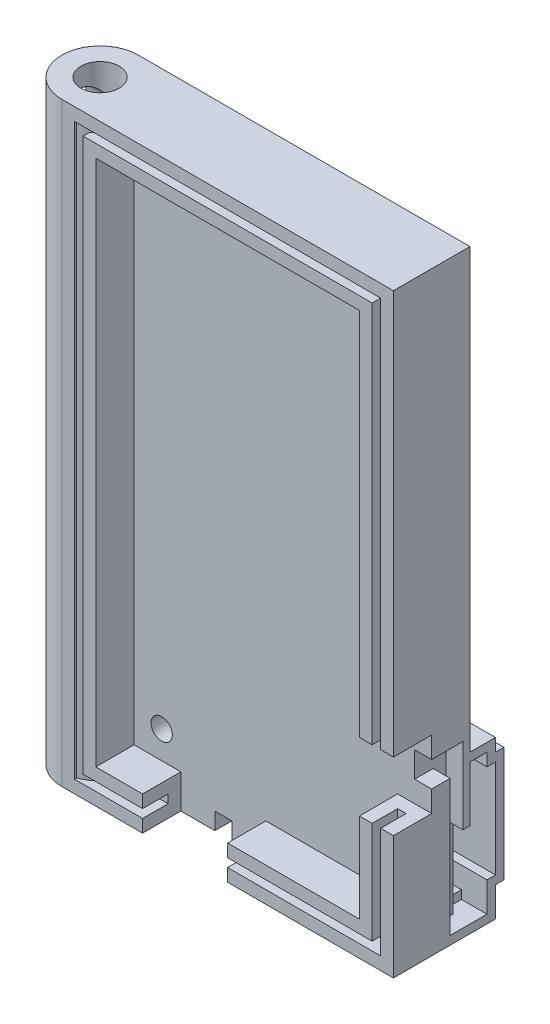
SolidWorks part; units mm, degrees
ref_plane "Front Plane" through (0, 0, 0) normal (0, 0, 1) x (1, 0, 0)
ref_plane "Top Plane" through (0, 0, 0) normal (0, 1, 0) x (1, 0, 0)
ref_plane "Right Plane" through (0, 0, 0) normal (1, 0, 0) x (0, 0, -1)
sketch "Sketch1" plane through (0, 0, 0) normal (0, 0, 1) x (1, 0, 0)
  line L1 (0, 0) -> (39, 0)
  line L2 (0, 0) -> (0, 70)
  line L3 (0, 70) -> (39, 70)
  line L4 (39, 0) -> (39, 70)
  dimension "D1" = 70
  dimension "D2" = 39
extrude "Base" add sketch "Sketch1" along normal blind 4.5
sketch "Sketch2" plane through (0, 0, 4.5) normal (0, 0, 1) x (1, 0, 0)
  line L0 (0, 70) -> (0, 0) construction
  line L1 (39, 70) -> (0, 70)
  line L2 (39, 70) -> (39, 66)
  line L3 (39, 66) -> (0, 66)
  line L4 (0, 70) -> (0, 66)
  line L5 (0, 0) -> (39, 0) construction
  line L6 (0, 66) -> (4, 66)
  line L7 (0, 66) -> (0, 0)
  line L8 (0, 0) -> (4, 0)
  line L9 (4, 66) -> (4, 0)
  line L10 (39, 0) -> (39, 70) construction
  line L11 (4, 0) -> (39, 0)
  line L12 (4, 0) -> (4, 4)
  line L13 (4, 4) -> (39, 4)
  line L14 (39, 0) -> (39, 4)
  line L16 (39, 66) -> (35, 66)
  line L17 (39, 66) -> (39, 4)
  line L18 (39, 4) -> (35, 4)
  line L19 (35, 66) -> (35, 4)
  line M6 (0, 70) -> (0, 0)
  line M7 (0, 0) -> (39, 0)
  line M8 (39, 0) -> (39, 70)
  line M9 (39, 70) -> (0, 70)
  dimension "D1" = 4
  dimension "D2" = 4
  dimension "D3" = 4
  dimension "D4" = 4
extrude "Walls" add sketch "Sketch2" along normal blind 4.5 contours L3 M8 M9 M6 | L3 L19 L13 M8 | L9 L3 M6 M7 | L13 L9 M7 M8 region at (19.5, 68, 4.5) region at (37, 35, 4.5) region at (2, 33, 4.5) region at (21.5, 2, 4.5)
sketch "Sketch3" plane through (0, 4, 0) normal (0, 1, 0) x (1, 0, 0)
  line L0 (4, -4.5) -> (35, -4.5) construction
  line L1 (9.5, -4.5) -> (19.5, -4.5)
  line L2 (9.5, -4.5) -> (9.5, -9)
  line L3 (9.5, -9) -> (19.5, -9)
  line L4 (19.5, -4.5) -> (19.5, -9)
  line L5 (4, -9) -> (35, -9) construction
  line L6 (4, -9) -> (4, -4.5) construction
  dimension "D1" = 5.5
  dimension "D2" = 15.5
extrude "PWR connector hole" cut sketch "Sketch3" against normal blind 4
sketch "Sketch4" plane through (35, 0, 0) normal (-1, 0, 0) x (0, 0, 1)
  line L0 (4.5, 66) -> (4.5, 4) construction
  line L1 (4.5, 14.5) -> (9, 14.5)
  line L2 (4.5, 14.5) -> (4.5, 22.5)
  line L3 (4.5, 22.5) -> (9, 22.5)
  line L4 (9, 14.5) -> (9, 22.5)
  line L5 (9, 66) -> (9, 4) construction
  line L6 (9, 4) -> (4.5, 4) construction
  dimension "D1" = 10.5
  dimension "D2" = 18.5
extrude "GPS connector hole" cut sketch "Sketch4" against normal blind 4
sketch "Sketch5" plane through (0, 0, 4.5) normal (0, 0, 1) x (1, 0, 0)
  line L0 (4, 4) -> (9.5, 4) construction
  line L1 (4, 66) -> (4, 4) construction
  line L2 (19.5, 66) -> (19.5, 4) construction
  line L3 (35, 66) -> (4, 66) construction
  line L5 (19.5, 35) -> (4, 35) construction
  line L6 (4, 66) -> (4, 4) construction
  circle A0 centre (7.25, 7.25) radius 1.25
  circle A1 centre (31.75, 7.25) radius 1.25
  circle A2 centre (7.25, 62.75) radius 1.25
  dimension "D1" = 3.25
  dimension "D3" = 2.5
  dimension "D2" = 3.25
extrude "Mounting holes" cut sketch "Sketch5" against normal blind 4
sketch "Sketch7" plane through (0, 0, 0) normal (0, 0, -1) x (-1, 0, 0)
  line L0 (-39, 0) -> (-39, 18.5) construction
  line L1 (-39, 0) -> (-39, 70) construction
  line L3 (-39, 1) -> (-8, 1)
  line L4 (-39, 1) -> (-39, 17.5)
  line L5 (-39, 17.5) -> (-8, 17.5)
  line L6 (-8, 1) -> (-8, 17.5)
  line L9 (0, 0) -> (-39, 0) construction
  line L10 (-39, 0) -> (-7, 0)
  line L11 (-7, 0) -> (-7, 18.5)
  line L12 (-7, 18.5) -> (-39, 18.5)
  line L13 (-39, 18.5) -> (-39, 17.5)
  line L14 (-39, 1) -> (-39, 0)
  line M8 (-39, 70) -> (-39, 0)
  line M9 (-39, 0) -> (0, 0)
  dimension "D1" = 18.5
  dimension "D2" = 1
  dimension "D3" = 16.5
  dimension "D4" = 31
  dimension "D5" = 32
  dimension "D6" = 18.5
extrude "GPS mount" add sketch "Sketch7" along normal blind 3 contours L11 L12 L5 L6 L3 M8 M9 region at (23.5, 0.6304, 0)
sketch "Sketch8" plane through (8, 0, 0) normal (1, 0, 0) x (0, 0, -1)
  line L0 (3, 17.5) -> (0, 17.5) construction
  line L1 (1, 17.5) -> (2, 17.5)
  line L2 (1, 17.5) -> (1, 16.5)
  line L3 (1, 16.5) -> (2, 16.5)
  line L4 (2, 17.5) -> (2, 16.5)
  line L5 (0, 1) -> (0, 17.5) construction
  line L6 (0, 9.25) -> (3, 9.25) construction
  line L7 (3, 1) -> (3, 17.5) construction
  line L8 (1, 2) -> (2, 2)
  line L9 (2, 1) -> (2, 2)
  line L10 (1, 1) -> (2, 1)
  line L11 (1, 1) -> (1, 2)
  dimension "D1" = 1
  dimension "D2" = 1
  dimension "D3" = 1
extrude "GPS rails" add sketch "Sketch8" along normal blind 28
sketch "Sketch9" plane through (8, 0, 0) normal (1, 0, 0) x (0, 0, -1)
  line L1 (3, 1) -> (2, 1)
  line L2 (3, 1) -> (3, 17.5)
  line L3 (3, 17.5) -> (2, 17.5)
  line L4 (2, 1) -> (2, 17.5)
extrude "GPS \"roof\"" add sketch "Sketch9" along normal blind 14
sketch "Sketch10" plane through (22, 0, 0) normal (1, 0, 0) x (0, 0, -1)
  line L0 (3, 1) -> (3, 17.5) construction
  line L1 (2, 17.5) -> (3, 17.5)
  line L2 (2, 17.5) -> (2, 16)
  line L3 (2, 16) -> (3, 16)
  line L4 (3, 17.5) -> (3, 16)
  line L6 (2, 1) -> (3, 1)
  line L7 (2, 1) -> (2, 4.5)
  line L8 (2, 4.5) -> (3, 4.5)
  line L9 (3, 1) -> (3, 4.5)
  dimension "D1" = 1.5
  dimension "D2" = 3.5
extrude "GPS \"roof" add sketch "Sketch10" along normal blind 17
sketch "Sketch18" plane through (0, 0, -3) normal (0, 0, -1) x (-1, 0, 0)
  line L0 (-22, 4.5) -> (-22, 16) construction
  line L1 (-39, 4.5) -> (-21, 4.5)
  line L2 (-39, 4.5) -> (-39, 3.5)
  line L3 (-39, 3.5) -> (-21, 3.5)
  line L4 (-21, 4.5) -> (-21, 3.5)
  dimension "D1" = 1
  dimension "D2" = 1
extrude "Chip roof1" add sketch "Sketch18" along normal blind 1
sketch "Sketch19" plane through (0, 4.5, 0) normal (0, 1, 0) x (1, 0, 0)
  line L0 (39, 4) -> (39, 2) construction
  line L1 (21, 4) -> (39, 4)
  line L2 (21, 4) -> (21, 3)
  line L3 (21, 3) -> (39, 3)
  line L4 (39, 4) -> (39, 3)
extrude "Chip roof2" add sketch "Sketch19" along normal blind 12.5
sketch "Sketch11" plane through (0, 0, 0) normal (0, 0, -1) x (-1, 0, 0)
  line L0 (0, 0) -> (-7, 0) construction
  line L1 (-4, 0) -> (-5, 0)
  line L2 (-4, 0) -> (-4, 21.5)
  line L3 (-4, 21.5) -> (-5, 21.5)
  line L4 (-5, 0) -> (-5, 21.5)
  line L5 (-7, 0) -> (-7, 18.5) construction
  line L7 (0, 70) -> (0, 0) construction
  line L8 (-5, 21.5) -> (-22, 21.5)
  line L9 (-5, 21.5) -> (-5, 20.5)
  line L10 (-5, 20.5) -> (-22, 20.5)
  line L11 (-22, 21.5) -> (-22, 20.5)
  line L12 (-7, 18.5) -> (-39, 18.5) construction
  line L13 (-28, 18.5) -> (-27, 18.5)
  line L14 (-28, 18.5) -> (-28, 21.5)
  line L15 (-28, 21.5) -> (-27, 21.5)
  line L16 (-27, 18.5) -> (-27, 21.5)
  line M5 (-7, 0) -> (0, 0)
  line M9 (-39, 18.5) -> (-7, 18.5)
  dimension "D1" = 1
  dimension "D2" = 2
  dimension "D3" = 21.5
  dimension "D4" = 1
  dimension "D5" = 22
  dimension "D6" = 5
  dimension "D7" = 1
  dimension "D8" = 3
extrude "PWR cable holder1" add sketch "Sketch11" along normal blind 3 contours L4 L2 L3 M5 | L8 L11 L10 L4 | L16 L15 L14 M9 region at (4.5, 10.75, 0) region at (13.5, 21, 0) region at (27.5, 20, 0)
sketch "Sketch12" plane through (0, 0, 0) normal (0, -1, 0) x (1, 0, 0)
  line L0 (19.5, 4.5) -> (9.5, 4.5) construction
  line L1 (5, 0) -> (15.5, 0)
  line L2 (5, 0) -> (5, 2)
  line L3 (5, 2) -> (15.5, 2)
  line L4 (15.5, 0) -> (15.5, 2)
  line L5 (9.5, 4.5) -> (9.5, 9) construction
  line L6 (13.5, 4.5) -> (15.5, 4.5)
  line L7 (13.5, 4.5) -> (13.5, 2)
  line L8 (13.5, 2) -> (15.5, 2)
  line L9 (15.5, 4.5) -> (15.5, 2)
  line L10 (19.5, 9) -> (19.5, 4.5) construction
  line M5 (19.5, 4.5) -> (9.5, 4.5)
  line M13 (5, 0) -> (7, 0)
  dimension "D1" = 2
  dimension "D2" = 4
  dimension "D3" = 4
  dimension "D4" = 0
extrude "PWR cable holder2" cut sketch "Sketch12" against normal blind 2 contours L1 L4 L3 L2 M13 | L9 L7 L3 M5 region at (10.25, 0, 1) region at (14.5, 0, 3.25)
sketch "Sketch13" plane through (39, 0, 0) normal (1, 0, 0) x (0, 0, -1)
  line L0 (-4.5, 22.5) -> (-4.5, 14.5) construction
  line L1 (-4.5, 20) -> (-2.3266, 20)
  line L2 (-4.5, 20) -> (-4.5, 17)
  line L3 (-4.5, 17) -> (-2.3266, 17)
  line L4 (-2.3266, 20) -> (-2.3266, 17)
  line L5 (-9, 22.5) -> (-4.5, 22.5) construction
  line L6 (-4.5, 14.5) -> (-9, 14.5) construction
  line L7 (-2.3266, 17) -> (-2.3266, 11)
  line L8 (0, 1) -> (-2.3266, 1)
  line L9 (0, 1) -> (0, 11)
  line L10 (0, 11) -> (-2.3266, 11)
  line L11 (-2.3266, 1) -> (-2.3266, 11)
  line L18 (-2.3266, 11) -> (-0.8266, 11)
  line L19 (-2.3266, 11) -> (-2.3266, 20)
  line L20 (-2.3266, 20) -> (-0.8266, 20)
  line L21 (-0.8266, 11) -> (-0.8266, 20)
  line M19 (-4.5, 22.5) -> (-4.5, 14.5)
  line M27 (0, 1) -> (0, 17.5)
  dimension "D1" = 2.5
  dimension "D2" = 2.5
  dimension "D3" = 10
  dimension "D4" = 1.5
  dimension "D5" = 2.3266
extrude "GPS cable holder" cut sketch "Sketch13" against normal blind 2 contours L4 L1 L3 M19 | L10 L21 L20 L4 L7 | L11 L8 L10 M27 region at (39, 18.5, 3.4133) region at (39, 15.5, 1.5766) region at (39, 6, 1.1633)
sketch "Sketch14" plane through (0, 0, 9) normal (0, 0, 1) x (1, 0, 0)
  line L1 (1.5, 1.5) -> (2.5, 1.5)
  line L2 (1.5, 1.5) -> (1.5, 68.5)
  line L3 (1.5, 68.5) -> (2.5, 68.5)
  line L4 (2.5, 1.5) -> (2.5, 68.5)
  line L5 (0, 70) -> (0, 0) construction
  line L6 (4, 66) -> (4, 4) construction
  line L7 (39, 70) -> (0, 70) construction
  line L8 (35, 66) -> (4, 66) construction
  line L9 (2.5, 68.5) -> (37.5, 68.5)
  line L10 (2.5, 68.5) -> (2.5, 67.5)
  line L11 (2.5, 67.5) -> (37.5, 67.5)
  line L12 (37.5, 68.5) -> (37.5, 67.5)
  line L13 (39, 22.5) -> (39, 70) construction
  line L14 (19.5, 70) -> (19.5, 0) construction
  line L15 (0, 35) -> (39, 35) construction
  line L16 (37.5, 68.5) -> (36.5, 68.5)
  line L17 (36.5, 1.5) -> (36.5, 68.5)
  line L18 (37.5, 1.5) -> (36.5, 1.5)
  line L19 (37.5, 1.5) -> (37.5, 68.5)
  line L20 (2.5, 2.5) -> (37.5, 2.5)
  line L21 (37.5, 1.5) -> (37.5, 2.5)
  line L22 (2.5, 1.5) -> (37.5, 1.5)
  line L23 (2.5, 1.5) -> (2.5, 2.5)
  line M15 (35, 22.5) -> (39, 22.5)
  line M20 (9.5, 0) -> (9.5, 4)
  dimension "D2" = 1.5
  dimension "D3" = 1.5
  dimension "D4" = 1.5
  dimension "D5" = 1.5
extrude "Lid mount" cut sketch "Sketch14" against normal blind 3 contours L1 L4 L3 L2 | L4 L22 L20 M20 | L22 L17 L20 M20 | L20 L17 L18 L19 | L17 L20 L19 M15 | L19 L11 L17 M15 | L11 L17 L9 L4 | L17 L11 L12 L9 region at (2, 35, 9) region at (6, 2, 9) region at (23, 2, 9) region at (19.5, 68, 9) region at (37, 2, 9) region at (37, 68, 9) region at (37, 45, 9) region at (37, 12.5, 9)
sketch "Sketch15" plane through (0, 0, 0) normal (0, -1, 0) x (1, 0, 0)
  line L0 (0, 9) -> (0, 0) construction
  circle A0 centre (0, 4.5) radius 4.5
extrude "Ballon mount" add sketch "Sketch15" against normal blind 70
sketch "Sketch16" plane through (0, 0, 0) normal (0, -1, 0) x (1, 0, 0)
  line L0 (0, 0) -> (0, 4.5) construction
  circle A0 centre (0, 4.5) radius 2.25
  dimension "D1" = 4.5
extrude "Balloon mount hole" cut sketch "Sketch16" against normal blind 70
sketch "Sketch17" plane through (0, 0, 9) normal (0, 0, 1) x (1, 0, 0)
  line L0 (35, 66) -> (4, 66) construction
  line L1 (4, 4) -> (6, 4)
  line L2 (4, 4) -> (4, 66)
  line L3 (4, 66) -> (6, 66)
  line L4 (6, 4) -> (6, 66)
  dimension "D1" = 2
extrude "Correction" cut sketch "Sketch17" against normal blind 4.5
ref_plane "Plane1" through (-4.5, 0, 0) normal (-1, 0, 0) x (0, 0, 1)
sketch "Sketch21" plane through (-4.5, 0, 0) normal (-1, 0, 0) x (0, 0, 1)
  line L0 (4.5, 0) -> (4.5, 4.5) construction
  line L1 (0, 0) -> (9, 0) construction
  line L2 (0, 35) -> (9, 35) construction
  line L3 (0, 70) -> (0, 0) construction
  line L4 (9, 70) -> (9, 0) construction
  circle A0 centre (4.5, 4.5) radius 2.25
  circle A1 centre (4.5, 65.5) radius 2.25
  dimension "D2" = 4.5
  dimension "D1" = 4.5
extrude "Safety mount" cut sketch "Sketch21" against normal blind 4.5
